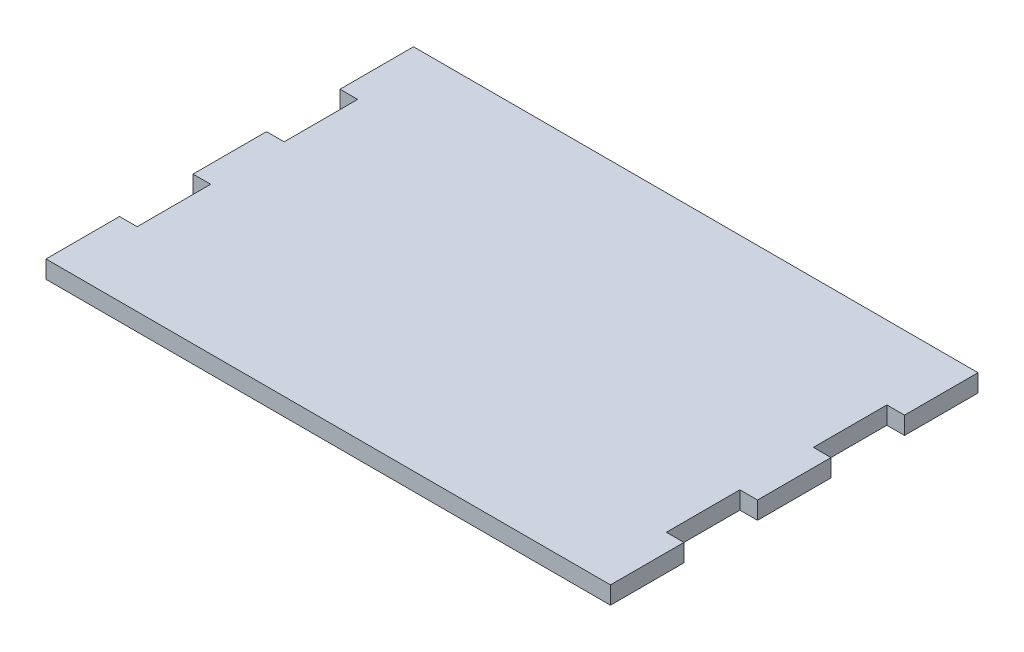
SolidWorks part; units mm, degrees
ref_plane "Front Plane" through (0, 0, 0) normal (0, 0, 1) x (1, 0, 0)
ref_plane "Top Plane" through (0, 0, 0) normal (0, 1, 0) x (1, 0, 0)
ref_plane "Right Plane" through (0, 0, 0) normal (1, 0, 0) x (0, 0, -1)
sketch "Sketch1" plane through (0, 0, 0) normal (0, 1, 0) x (1, 0, 0)
  line L0 (0, 0) -> (180, 0)
  line L1 (0, 100) -> (180, 100)
  line L2 (0, 0) -> (0, 100)
  line L4 (180, 0) -> (180, 100)
sketch "Sketch2" plane through (0, 0, 0) normal (0, 1, 0) x (1, 0, 0)
  line L1 (0, -6) -> (180, -6)
  line L2 (0, -6) -> (0, 106)
  line L3 (0, 106) -> (180, 106)
  line L4 (180, -6) -> (180, 106)
sketch "Sketch3" plane through (0, 0, 0) normal (0, 1, 0) x (1, 0, 0)
  line L1 (-6, -11) -> (186, -11)
  line L2 (-6, -11) -> (-6, 114)
  line L3 (-6, 114) -> (186, 114)
  line L4 (186, -11) -> (186, 114)
sketch "Sketch4" plane through (0, 0, 0) normal (0, 1, 0) x (1, 0, 0)
  line L0 (-6, 114) -> (-6, 89)
  line L1 (-6, -11) -> (-6, 114) construction
  line L2 (-6, 89) -> (0, 89)
  line L3 (0, 0) -> (0, 100) construction
  line L4 (0, 89) -> (0, 64)
  line L5 (0, 64) -> (-6, 64)
  line L6 (-6, 64) -> (-6, 39)
  line L7 (-6, 39) -> (0, 39)
  line L8 (0, 39) -> (0, 14)
  line L9 (0, 14) -> (-6, 14)
  line L10 (-6, 14) -> (-6, -11)
  line L11 (-6, -11) -> (-10, -11)
  line L12 (-10, -11) -> (-10, 114)
  line L13 (-10, 114) -> (-6, 114)
  line L26 (190, 114) -> (186, 114)
  line L27 (190, -11) -> (190, 114)
  line L28 (186, -11) -> (190, -11)
  line L29 (186, 14) -> (186, -11)
  line L30 (180, 14) -> (186, 14)
  line L31 (180, 39) -> (180, 14)
  line L32 (186, 39) -> (180, 39)
  line L33 (186, 64) -> (186, 39)
  line L34 (180, 64) -> (186, 64)
  line L35 (180, 89) -> (180, 64)
  line L36 (186, 89) -> (180, 89)
  line L37 (186, 114) -> (186, 89)
extrude "Boss-Extrude1" add sketch "Sketch3" along normal blind 6
extrude "Cut-Extrude1" cut sketch "Sketch4" along normal blind 6
ref_plane "Plane1" through (0, 6, 0) normal (0, 1, 0) x (1, 0, 0)
sketch "Sketch5" plane through (0, 6, 0) normal (0, 1, 0) x (1, 0, 0)
  line L0 (0, 0) -> (180, 0)
  line L1 (0, 100) -> (180, 100)
  line L2 (0, 0) -> (0, 100)
  line L4 (180, 0) -> (180, 100)
sketch "Sketch7" plane through (0, 6, 0) normal (0, 1, 0) x (1, 0, 0)
  line L1 (0, -6) -> (180, -6)
  line L2 (0, -6) -> (0, 106)
  line L3 (0, 106) -> (180, 106)
  line L4 (180, -6) -> (180, 106)
